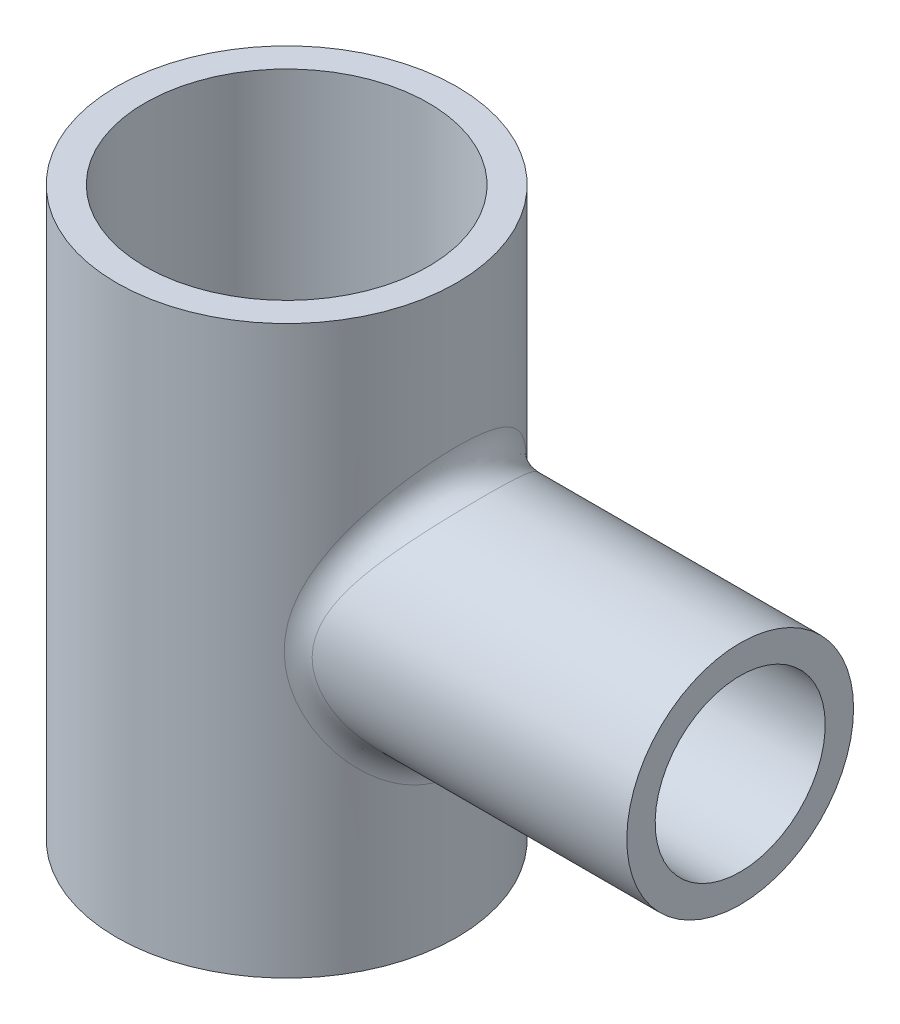
SolidWorks part; units mm, degrees
ref_plane "Front Plane" through (0, 0, 0) normal (0, 0, 1) x (1, 0, 0)
ref_plane "Top Plane" through (0, 0, 0) normal (0, 1, 0) x (1, 0, 0)
ref_plane "Right Plane" through (0, 0, 0) normal (1, 0, 0) x (0, 0, -1)
sketch "Sketch1" plane through (0, 0, 0) normal (0, 1, 0) x (1, 0, 0)
  line L0 (0, -55) -> (0, 55) construction
  circle A0 centre (0, 0) radius 30
  dimension "D1" = 60
extrude "Boss-Extrude1" add sketch "Sketch1" along normal mid plane 100
sketch "Sketch2" plane through (0, 0, 0) normal (1, 0, 0) x (0, 0, -1)
  circle A0 centre (0, 0) radius 20
  dimension "D1" = 40
extrude "Boss-Extrude2" add sketch "Sketch2" along normal blind 80
shell "Shell1" thickness 5 removed face at (0, -50, 30) removed face at (80, 0, -20) removed face at (0, 50, 30)
fillet "Fillet1" radius 5 1 edges at (22.7425, 4.1499, -19.5647)
